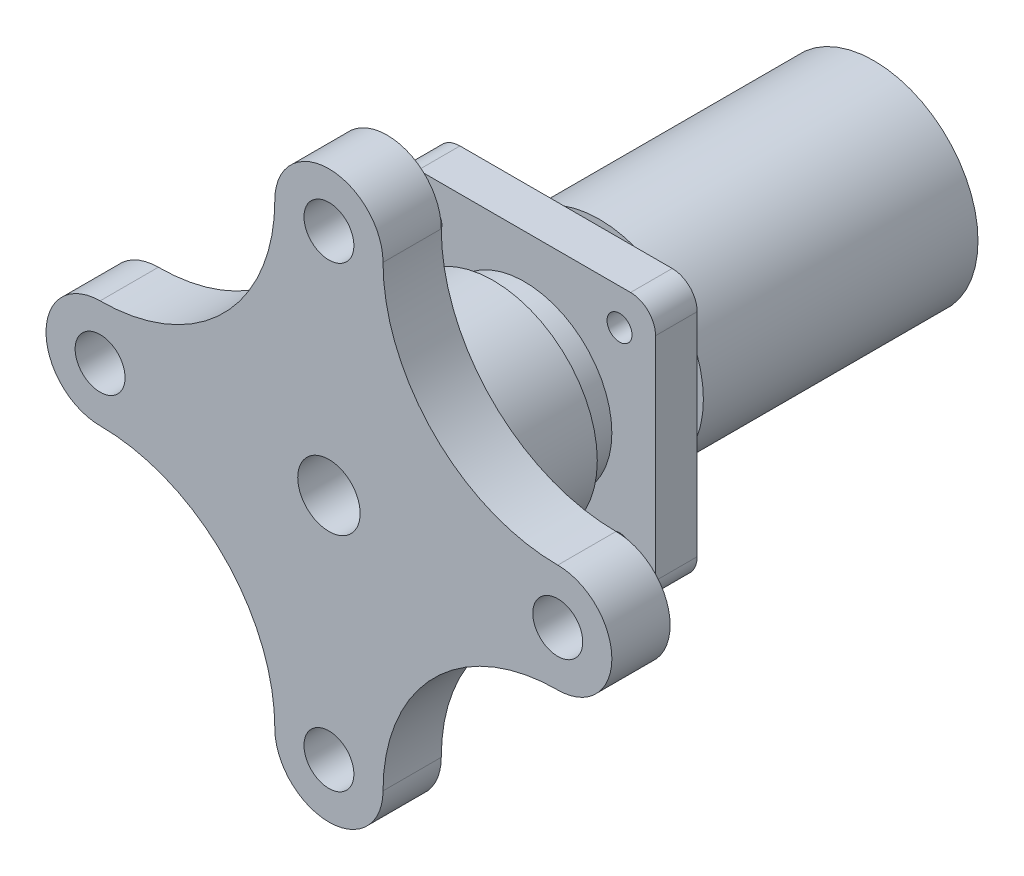
SolidWorks part; units mm, degrees
ref_plane "Front Plane" through (0, 0, 0) normal (0, 0, 1) x (1, 0, 0)
ref_plane "Top Plane" through (0, 0, 0) normal (0, 1, 0) x (1, 0, 0)
ref_plane "Right Plane" through (0, 0, 0) normal (1, 0, 0) x (0, 0, -1)
sketch "Sketch1" plane through (0, 0, 0) normal (0, 0, 1) x (1, 0, 0)
  circle A0 centre (0, 0) radius 12.75
  circle A1 centre (0, 0) radius 25
  dimension "D1" = 25.5
  dimension "D2" = 50
extrude "Boss-Extrude1" add sketch "Sketch1" along normal blind 117
ref_plane "disk_plane" through (0, 0, 74) normal (0, 0, -1) x (-1, 0, 0)
sketch "Sketch2" plane through (0, 0, 74) normal (0, 0, -1) x (-1, 0, 0)
  line L0 (0, 0) -> (46.4229, 0) construction
  line L1 (-25.5, -31.5) -> (25.5, -31.5)
  line L2 (-31.5, -25.5) -> (-31.5, 25.5)
  line L3 (-25.5, 31.5) -> (25.5, 31.5)
  line L4 (31.5, -25.5) -> (31.5, 25.5)
  line L5 (-31.5, -31.5) -> (31.5, 31.5) construction
  line L6 (-31.5, 31.5) -> (31.5, -31.5) construction
  circle A0 centre (22.8466, 22.8466) radius 3
  circle A1 centre (-22.8466, -22.8466) radius 3
  circle A2 centre (22.8466, -22.8466) radius 3
  circle A3 centre (-22.8466, 22.8466) radius 3
  arc A4 (25.5, -31.5) -> (31.5, -25.5) centre (25.5, -25.5) ccw
  arc A5 (-25.5, -31.5) -> (-31.5, -25.5) centre (-25.5, -25.5) cw
  arc A6 (-31.5, 25.5) -> (-25.5, 31.5) centre (-25.5, 25.5) cw
  arc A7 (25.5, 31.5) -> (31.5, 25.5) centre (25.5, 25.5) cw
  circle A8 centre (0, 0) radius 25
  circle A10 centre (0, 0) radius 25 construction
  point P0 (0, 0)
  dimension "D3" = 6
  dimension "D4" = 6
  dimension "D1" = 63
  dimension "D2" = 63
  dimension "D5" = 32.31
extrude "Boss-Extrude2" add sketch "Sketch2" against normal blind 10
sketch "Sketch3" plane through (0, 0, 117) normal (0, 0, 1) x (1, 0, 0)
  line L0 (0, 42) -> (0, 55) construction
  line L1 (0, 0) -> (55, 0) construction
  line L2 (0, 55) -> (21.233, 55) construction
  line L3 (55, 0) -> (55, 23.4869) construction
  line L4 (13, 55) -> (13, 33.7853) construction
  line L5 (55, 13) -> (81.8117, 13) construction
  circle A0 centre (0, 0) radius 55 construction
  circle A1 centre (0, 55) radius 6
  circle A2 centre (55, 0) radius 6
  circle A3 centre (0, -55) radius 6
  circle A4 centre (-55, 0) radius 6
  arc A5 (12.9089, 53.4636) -> (-12.9089, 53.4636) centre (0, 55) ccw
  arc A6 (53.4636, -12.9089) -> (53.4636, 12.9089) centre (55, 0) ccw
  arc A7 (-12.9089, -53.4636) -> (12.9089, -53.4636) centre (0, -55) ccw
  arc A8 (-53.4636, 12.9089) -> (-53.4636, -12.9089) centre (-55, 0) ccw
  arc A9 (13, 55) -> (55, 13) centre (55, 55) ccw
  arc A10 (55, -13) -> (13, -55) centre (55, -55) ccw
  arc A11 (-13, -55) -> (-55, -13) centre (-55, -55) ccw
  arc A12 (-55, 13) -> (-13, 55) centre (-55, 55) ccw
  circle A13 centre (0, 0) radius 7.5
  point P10 (13, 55)
  point P15 (0, 0)
  point P16 (55, 13)
  point P23 (0, 0)
  point P41 (0, 0)
  circle M1 centre (0, 0) radius 25
  circle M2 centre (0, 0) radius 12.75
  dimension "D1" = 110
  dimension "D2" = 4
  dimension "D3" = 12
  dimension "D5" = 26
  dimension "D7" = 15
  dimension "D6" = 4
  dimension "D4" = 4
extrude "Boss-Extrude3" add sketch "Sketch3" along normal blind 14 contours A12 A8 A11 A7 A10 A6 A9 A5 A4 A3 A2 A1 M1 | M1 M2 | A13 M2 region at (23.9415, 23.9415, 117) region at (-24.2929, 0, 117) region at (-12.3894, 0, 117)
sketch "Sketch4" plane through (0, 0, 74) normal (0, 0, -1) x (-1, 0, 0)
  circle A0 centre (22.8466, 22.8466) radius 9
  circle A1 centre (22.8466, -22.8466) radius 9
  circle A2 centre (-22.8466, -22.8466) radius 9
  circle A3 centre (-22.8466, 22.8466) radius 9
  point P12 (0, 0)
  dimension "D2" = 18
  dimension "D1" = 4
sketch "Sketch5" plane through (0, 0, 84) normal (0, 0, 1) x (1, 0, 0)
  circle A0 centre (22.8466, 22.8466) radius 9
  circle A1 centre (22.8466, -22.8466) radius 9
  circle A2 centre (-22.8466, -22.8466) radius 9
  circle A3 centre (-22.8466, 22.8466) radius 9
  point P12 (0, 0)
  dimension "D1" = 18
  dimension "D2" = 4
fillet "Fillet3" radius 6 1 edges at (25, 0, 117)
ref_plane "Plane2" through (0, 0, 74) normal (0, 0, -1) x (-1, 0, 0)
sketch "Sketch6" plane through (0, 0, 74) normal (0, 0, -1) x (-1, 0, 0)
  circle A0 centre (0, 0) radius 20
  circle A1 centre (0, 0) radius 7.5
  dimension "D1" = 15
extrude "Boss-Extrude4" add sketch "Sketch6" against normal up to surface and the other way blind 17.5 up to face at (31, 0, 117)
sketch "Sketch7" plane through (0, 0, 0) normal (0, 0, -1) x (-1, 0, 0)
  circle A0 centre (0, 0) radius 27.5
ref_plane "Plane4" through (0, 0, 56.75) normal (0, 0, -1) x (-1, 0, 0)
sketch "Sketch11" plane through (0, 0, 74) normal (0, 0, -1) x (-1, 0, 0)
  circle A0 centre (0, 0) radius 27.5
  circle A1 centre (0, 0) radius 21
  dimension "D1" = 42
extrude "nut_groove" cut sketch "Sketch11" along normal blind 8
sketch "Sketch13" plane through (0, 0, 56.5) normal (0, 0, -1) x (-1, 0, 0)
  circle A0 centre (0, 0) radius 12
  circle A1 centre (0, 0) radius 22.5
ref_plane "plane" through (0, 0, 84) normal (0, 0, 1) x (1, 0, 0)
sketch "Sketch15" plane through (0, 0, 84) normal (0, 0, 1) x (1, 0, 0)
  circle A0 centre (0, 0) radius 21
  circle A1 centre (0, 0) radius 27.5
  dimension "D1" = 42
extrude "bolt_groove" cut sketch "Sketch15" along normal blind 7.5
